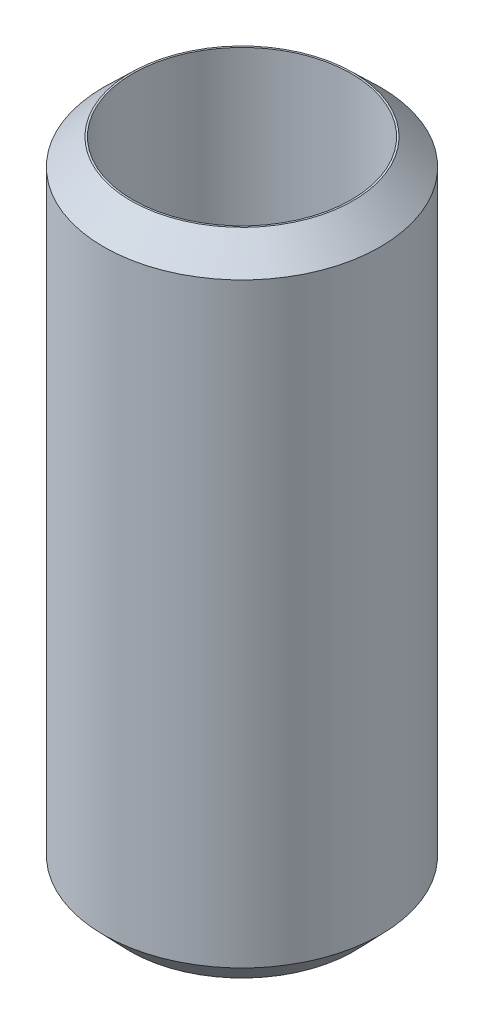
SolidWorks part; units mm, degrees
ref_plane "Front Plane" through (0, 0, 0) normal (0, 0, 1) x (1, 0, 0)
ref_plane "Top Plane" through (0, 0, 0) normal (0, 1, 0) x (1, 0, 0)
ref_plane "Right Plane" through (0, 0, 0) normal (1, 0, 0) x (0, 0, -1)
sketch "Sketch1" plane through (0, 0, 0) normal (0, 1, 0) x (1, 0, 0)
  circle A0 centre (0, 0) radius 22.5
  dimension "SHAFT_OD" = 45
extrude "Boss-Extrude1" add sketch "Sketch1" along normal blind 105.6114
sketch "Sketch2" plane through (0, 0, 0) normal (0, 1, 0) x (1, 0, 0)
  circle A0 centre (0, 0) radius 17.7786
  dimension "BORE_D" = 35.5572
extrude "Cut-Extrude1" cut sketch "Sketch2" along normal through all
chamfer "Chamfer1" distance 4.2728 angle 46.073 2 edges at (0, 105.6114, 22.5) (0, 0, 22.5) first distance on face at (0, 105.6114, 22.5) first distance on face at (0, 0, 17.7786)
